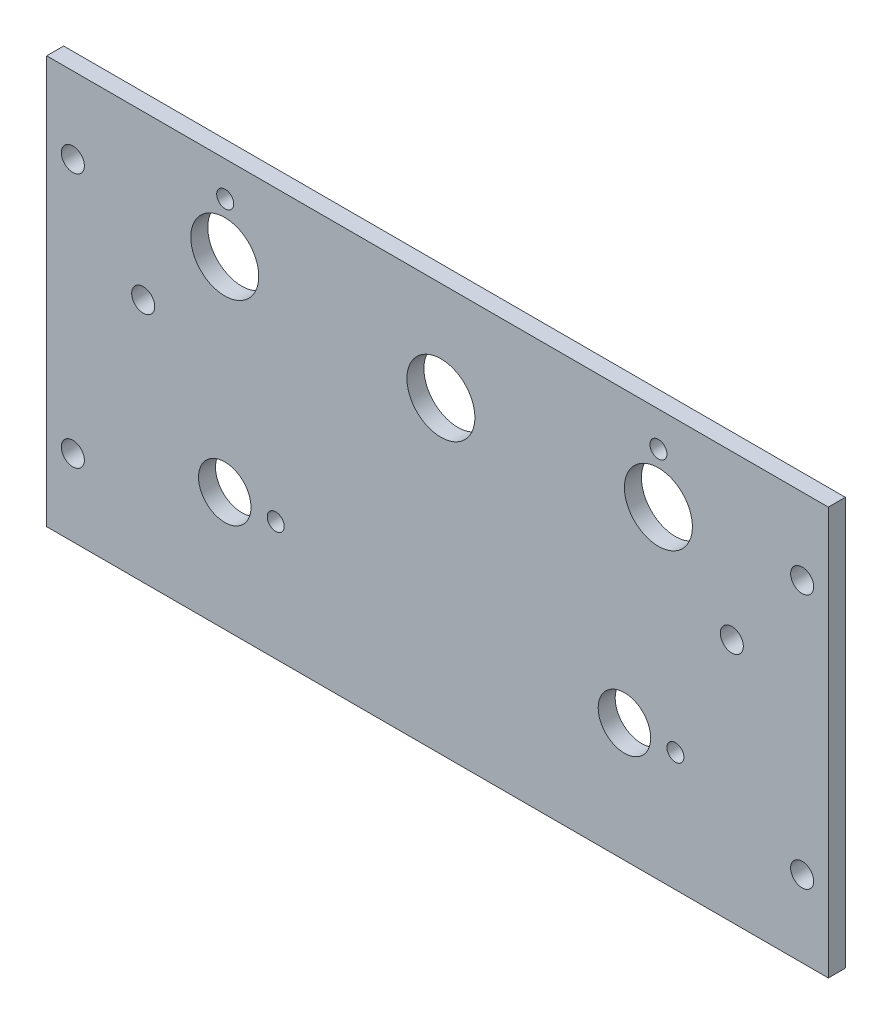
SolidWorks part; units mm, degrees
ref_plane "Front Plane" through (0, 0, 0) normal (0, 0, 1) x (1, 0, 0)
ref_plane "Top Plane" through (0, 0, 0) normal (0, 1, 0) x (1, 0, 0)
ref_plane "Right Plane" through (0, 0, 0) normal (1, 0, 0) x (0, 0, -1)
sketch "Sketch1" plane through (0, 0, 0) normal (0, 0, 1) x (1, 0, 0)
  line L4 (0, 76.2) -> (-146.05, 76.2)
  line L5 (-146.05, 76.2) -> (-146.05, 0)
  line L6 (-146.05, 0) -> (0, 0)
  line L7 (0, 0) -> (0, 76.2)
  line L8 (0, 76.2) -> (-146.05, 76.2)
  line L9 (-146.05, 76.2) -> (-146.05, 0)
  line L10 (-146.05, 0) -> (0, 0)
  line L11 (0, 0) -> (0, 76.2)
  dimension "D1" = 0
extrude "Backplate Body" add sketch "Sketch1" against normal blind 3.175
hole_wizard "#6 Panel Screw Holes" positions "Sketch3" profile "Sketch2" hole size "#6" standard "ANSI Inch" end condition through all
sketch "Sketch3" plane through (0, 0, -3.175) normal (0, 0, -1) x (-1, 0, 0)
  point P0 (4.8895, 61.9125)
  point P3 (4.8895, 14.2875)
  point P6 (141.1605, 14.2875)
  point P9 (141.1605, 61.9125)
  point P12 (128.016, 45.72)
  point P15 (18.034, 45.72)
sketch "Sketch2" plane through (-4.8895, 61.9125, -3.175) normal (1, 0, 0) x (0, 1, 0)
  line L0 (0, 0) -> (0, 3.175)
  line L1 (0, 3.175) -> (2.1526, 3.175)
  line L2 (2.1526, 3.175) -> (2.1526, 0)
  line L5 (2.1526, 0) -> (0, 0)
  line L11 (0, -6.35) -> (0, 107.95) construction
  dimension "Thru Hole Dia." = 4.3053
  dimension "Thru Hole Depth" = 3.175
hole_wizard "1/2 Switch Holes" positions "Sketch5" profile "Sketch4" hole size "1/2" standard "ANSI Inch" end condition through all
sketch "Sketch5" plane through (0, 0, -3.175) normal (0, 0, -1) x (-1, 0, 0)
  point P0 (31.75, 60.325)
  point P3 (72.39, 57.658)
  point P6 (112.776, 60.325)
sketch "Sketch4" plane through (-31.75, 60.325, -3.175) normal (1, 0, 0) x (0, 1, 0)
  line L0 (0, 0) -> (0, 3.175)
  line L1 (0, 3.175) -> (6.35, 3.175)
  line L2 (6.35, 3.175) -> (6.35, 0)
  line L5 (6.35, 0) -> (0, 0)
  line L11 (0, -6.35) -> (0, 107.95) construction
  dimension "Thru Hole Dia." = 12.7
  dimension "Thru Hole Depth" = 3.175
hole_wizard "1/8 (0.125) Switch Anti-Rotation Holes" positions "Sketch9" profile "Sketch8" hole size "1/8" standard "ANSI Inch" end condition through all
sketch "Sketch9" plane through (0, 0, -3.175) normal (0, 0, -1) x (-1, 0, 0)
  point P0 (31.75, 69.6995)
  point P2 (112.6954, 69.6995)
  point P7 (0, 0)
  point P8 (0, 0)
sketch "Sketch8" plane through (-31.75, 69.6995, -3.175) normal (1, 0, 0) x (0, 1, 0)
  line L0 (0, 0) -> (0, 3.175)
  line L1 (0, 3.175) -> (1.5875, 3.175)
  line L2 (1.5875, 3.175) -> (1.5875, 0)
  line L5 (1.5875, 0) -> (0, 0)
  line L11 (0, -6.35) -> (0, 107.95) construction
  dimension "Thru Hole Dia." = 3.175
  dimension "Thru Hole Depth" = 3.175
hole_wizard "3/8 (0.375) Rotary Switch Holes" positions "Sketch7" profile "Sketch6" hole size "3/8" standard "ANSI Inch" end condition through all
sketch "Sketch7" plane through (0, 0, -3.175) normal (0, 0, -1) x (-1, 0, 0)
  point P0 (38.1, 22.225)
  point P3 (112.776, 22.225)
sketch "Sketch6" plane through (-38.1, 22.225, -3.175) normal (1, 0, 0) x (0, 1, 0)
  line L0 (0, 0) -> (0, 3.175)
  line L1 (0, 3.175) -> (4.9022, 3.175)
  line L2 (4.9022, 3.175) -> (4.9022, 0)
  line L5 (4.9022, 0) -> (0, 0)
  line L11 (0, -6.35) -> (0, 107.95) construction
  dimension "Thru Hole Dia." = 9.8044
  dimension "Thru Hole Depth" = 3.175
sketch "Sketch11" plane through (0, 0, 0) normal (0, 0, 1) x (1, 0, 0)
  line L0 (-112.776, 22.225) -> (-103.251, 22.225) construction
  line L1 (-38.1, 22.225) -> (-28.575, 22.225) construction
  line L2 (-112.776, 22.225) -> (-112.776, 35.2439) construction
  line L3 (-38.1, 22.225) -> (-38.1, 35.2439) construction
  circle A0 centre (-103.251, 22.225) radius 1.5875
  circle A1 centre (-28.575, 22.225) radius 1.5875
  point P5 (-38.1, 35.2439)
  dimension "D2" = 3.175
  dimension "D4" = 3.175
  dimension "D1" = 9.525
  dimension "D3" = 9.525
  dimension "D5" = 270
  dimension "D6" = 270
extrude "Rotary Switch Anti-Rotation Holes" cut sketch "Sketch11" against normal through all and the other way through all
